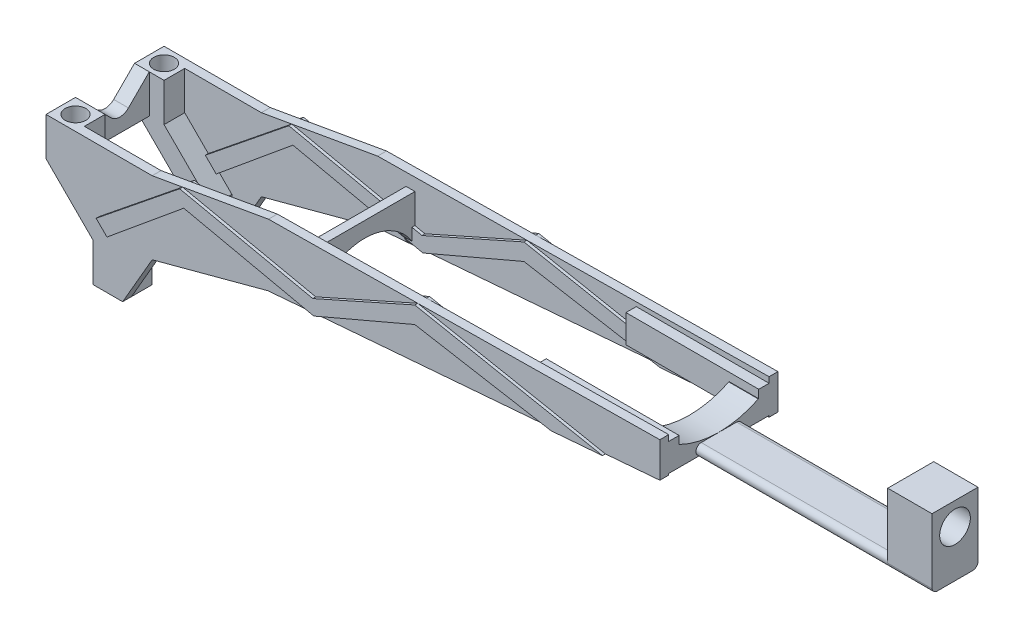
SolidWorks part; units mm, degrees
note: The reader was unsure of these and kept them because the rebuilt part matched: shared geometry of "草图5<8>", "草图18<3>", "草图24<4>".
ref_plane "前视基准面" through (0, 0, 0) normal (0, 0, 1) x (1, 0, 0)
ref_plane "上视基准面" through (0, 0, 0) normal (0, 1, 0) x (1, 0, 0)
ref_plane "右视基准面" through (0, 0, 0) normal (1, 0, 0) x (0, 0, -1)
sketch "草图1" plane through (0, 0, 0) normal (0, 0, 1) x (1, 0, 0)
  line L0 (0, 0) -> (0, -6.5)
  line L1 (0, -6.5) -> (7.9903, -14.4903)
  line L2 (7.9903, -14.4903) -> (7.9903, -20.9903)
  line L3 (7.9903, -20.9903) -> (12.9903, -20.9903)
  line L4 (12.9903, -20.9903) -> (12.9903, -14.4903)
  line L5 (12.9903, -14.4903) -> (5, -6.5)
  line L6 (5, -6.5) -> (5, 0)
  line L7 (0, 0) -> (5, 0)
extrude "凸台-拉伸1" add sketch "草图1" along normal blind 5 contours L7 L6 L5 L4 L3 L2 L1 L0
sketch "草图2" plane through (0, 0, 0) normal (0, 1, 0) x (1, 0, 0)
  line L0 (5, -5) -> (0, 0)
  line L3 (5, 0) -> (0, -5)
  circle A1 centre (2.5, -2.5) radius 1.75
extrude "切除-拉伸1" cut sketch "草图2" against normal blind 15
sketch "草图3" plane through (0, -20.9903, 0) normal (0, -1, 0) x (1, 0, 0)
  line L0 (7.9903, 5) -> (12.9903, 0)
  line L1 (12.9903, 5) -> (12.9903, 0) construction
  line L2 (7.9903, 0) -> (12.9903, 0) construction
  line L3 (7.9903, 0) -> (12.9903, 5)
  circle A1 centre (10.4903, 2.5) radius 1.75
sketch "草图5" plane through (0, 0, 5) normal (0, 0, 1) x (1, 0, 0)
  line L0 (12.9903, -20.9903) -> (17.9903, -12.3301)
  line L1 (17.9903, -12.3301) -> (37.5931, -7.0775)
  line L2 (37.5931, -7.0775) -> (107.0425, -1.4321)
  line L3 (5, 0) -> (17.9903, 0)
  line L4 (17.9903, 0) -> (37.6865, 3.473)
  line L5 (37.6865, 3.473) -> (107.0425, 4.3077)
  line L6 (107.0425, 4.3077) -> (107.0425, -1.4321)
  line L8 (87.8993, -2.9882) -> (94.7793, -2.429)
  line L14 (8.9952, -10.4952) -> (23.1388, 0.9078)
  line L17 (12.9903, -20.9903) -> (12.9903, -14.4903)
  line L18 (12.9903, -14.4903) -> (5, -6.5)
  line L19 (5, -6.5) -> (5, 0)
  line L20 (12.9903, -20.9903) -> (12.9903, -14.4903) construction
  line L22 (23.1388, 0.9078) -> (45.6985, -3.9198)
  line L23 (45.6985, -3.9198) -> (62.9747, 3.7773)
  line L24 (62.9747, 3.7773) -> (94.7793, -2.429)
  line L25 (10.8301, -12.3301) -> (23.8381, -1.5907)
  line L26 (23.8381, -1.5907) -> (45.8659, -6.405)
  line L27 (45.8659, -6.405) -> (62.9747, 0.9078)
  line L28 (62.9747, 0.9078) -> (86.0701, -3.1369)
extrude "凸台-拉伸2" add sketch "草图5" against normal blind 1.5 separate body
ref_plane "基准面5" through (0, 0, -10) normal (0, 0, -1) x (-1, 0, 0)
extrude "凸台-拉伸9" add sketch "草图5<8>" along normal blind 0.5 and the other way blind 2 contours L27 L28 L2 L24 L23 L22 L14 L18 L25 L26
sketch "草图5<8>" plane through (0, 0, 5) normal (0, 0, 1) x (1, 0, 0) same geometry as "草图5"
extrude "切除-拉伸6" cut sketch "草图3" against normal blind 6.5 contours A1
sketch "草图15" plane through (0, 0, -10) normal (0, 0, -1) x (-1, 0, 0)
  line L0 (-12.9903, -20.9903) -> (-7.9903, -20.9903)
  line L1 (-7.9903, -20.9903) -> (-7.9903, -14.4903)
  line L2 (-7.9903, -14.4903) -> (0, -6.5)
  line L3 (0, -6.5) -> (0, 0)
  line L4 (0, 0) -> (-5, 0)
  line L5 (-5, 0) -> (-17.9903, 0) construction
  line L6 (-5, -6.5) -> (-5, 0) construction
  line L7 (-5, 0) -> (-5, -6.5)
  line L8 (-5, -6.5) -> (-12.9903, -14.4903)
  line L9 (-12.9903, -14.4903) -> (-12.9903, -20.9903)
extrude "凸台-拉伸10" add sketch "草图15" along normal blind 5 separate body contours L9 L0 L1 L2 L3 L4 L7 L8
sketch "草图16" plane through (0, 0, 0) normal (0, 1, 0) x (1, 0, 0)
  line L0 (0, 15) -> (5, 10)
  line L1 (7.1447, 10) -> (-7.1447, 10) construction
  line L2 (5, 15) -> (5, 10) construction
  line L3 (5, 15) -> (0, 10)
  circle A0 centre (2.5, 12.5) radius 1.75
extrude "切除-拉伸7" cut sketch "草图16" against normal blind 15 contours L3 A0 L0 | L0 A0 L3 | L3 A0 L0 | L0 A0 L3
sketch "草图17" plane through (0, -20.9903, 0) normal (0, -1, 0) x (1, 0, 0)
  line L0 (7.9903, -15) -> (12.9903, -10)
  line L2 (-7.1447, -10) -> (7.1447, -10) construction
  line L3 (12.9903, -15) -> (7.9903, -10)
  circle A0 centre (10.4903, -12.5) radius 1.75
sketch "草图18" plane through (0, 0, -15) normal (0, 0, -1) x (-1, 0, 0)
  line L0 (-12.9903, -20.9903) -> (-17.9903, -12.3301)
  line L1 (-7.9903, -20.9903) -> (-12.9903, -20.9903) construction
  line L2 (-17.9903, -12.3301) -> (-37.5931, -7.0775)
  line L3 (-37.5931, -7.0775) -> (-107.0425, -1.4321)
  line L4 (-107.0425, -1.4321) -> (-107.0425, 4.3077)
  line L6 (-107.0425, 4.3077) -> (-37.6865, 3.473)
  line L7 (-37.6865, 3.473) -> (-17.9903, 0)
  line L8 (-17.9903, 0) -> (-5, 0)
  line L9 (-5, 0) -> (-5, -6.5)
  line L10 (-5, -6.5) -> (-12.9903, -14.4903)
  line L11 (-12.9903, -14.4903) -> (-12.9903, -20.9903)
  line L12 (-94.7793, -2.429) -> (-62.9747, 3.7773)
  line L13 (-62.9747, 3.7773) -> (-45.6985, -3.9198)
  line L14 (-45.6985, -3.9198) -> (-23.1388, 0.9078)
  line L15 (-23.1388, 0.9078) -> (-8.9952, -10.4952)
  line L16 (-86.0701, -3.1369) -> (-62.9747, 0.9078)
  line L17 (-62.9747, 0.9078) -> (-45.8659, -6.405)
  line L18 (-45.8659, -6.405) -> (-23.8381, -1.5907)
  line L19 (-23.8381, -1.5907) -> (-10.8301, -12.3301)
  line M11 (-5, -6.5) -> (-12.9903, -14.4903)
  line M12 (-12.9903, -14.4903) -> (-12.9903, -20.9903)
  line M18 (-5, 0) -> (-5, -6.5)
extrude "凸台-拉伸11" add sketch "草图18" against normal blind 1.5 contours L3 L12 L6 L4 | L17 L16 L3 | L13 L14 L7 L6 | L7 L15 L8 M11 M18 | L19 L18 L3 L2 L0 M12 M11
extrude "凸台-拉伸12" add sketch "草图18<3>" along normal blind 0.5 and the other way blind 2 contours L18 L19 L10 L15 L14 L13 L12 L3 L16 L17
sketch "草图18<3>" plane through (0, 0, -15) normal (0, 0, -1) x (-1, 0, 0) same geometry as "草图18"
extrude "切除-拉伸8" cut sketch "草图17" against normal blind 6.5 contours A0
sketch "草图19" plane through (0, 0, 0) normal (-1, 0, 0) x (0, 0, 1)
  line L0 (-10, 0) -> (-6.4645, -3.5355)
  line L1 (-10, 0) -> (-10, -6.5)
  line L2 (-10, 7.1447) -> (-10, -7.1447) construction
  line L3 (0, 0) -> (-3.5355, -3.5355)
  line L4 (-10, -6.5) -> (0, -6.5)
  line L5 (0, -6.5) -> (0, 0)
  arc A1 (-6.4645, -3.5355) -> (-3.5355, -3.5355) centre (-5, -2.0711) ccw
extrude "凸台-拉伸13" add sketch "草图19" against normal blind 2.5
ref_plane "基准面7" through (42.5, 0, 0) normal (1, 0, 0) x (0, 0, -1)
sketch "草图21" plane through (42.5, 0, 0) normal (1, 0, 0) x (0, 0, -1)
  line L0 (-3.5, 1.4378) -> (13.5, 1.4378)
  line L1 (-3.5, 4.3077) -> (-3.5, -1.4321) construction
  line L3 (13.5, -1.4321) -> (13.5, 4.3077) construction
  line L4 (-3.5, 1.4378) -> (-3.5, -6.5622)
  line L5 (-3.5, -6.405) -> (-3.5, -3.1369) construction
  line L6 (-3.5, -1.5907) -> (-3.5, -12.3301) construction
  line L7 (13.5, 1.4378) -> (13.5, -6.5622)
  line L8 (13.5, -1.5907) -> (13.5, -12.3301) construction
  line L9 (-3.5, -6.5622) -> (13.5, -6.5622)
  line L10 (5, -6.5622) -> (5, -10.5664)
  circle A0 centre (5, -10.5664) radius 9.408
extrude "凸台-拉伸14" add sketch "草图21" along normal blind 1.5 contours A0 L7 L0 L4
ref_plane "基准面8" through (104, 0, 0) normal (1, 0, 0) x (0, 0, -1)
sketch "草图24" plane through (104, 0, 0) normal (1, 0, 0) x (0, 0, -1)
  line L0 (-3.5, 1.9102) -> (13.5, 1.9102)
  line L1 (13.5, -2.429) -> (13.5, 3.7773) construction
  line L2 (13.5, 1.9102) -> (13.5, -1.4321)
  line L3 (-3.5, 4.3077) -> (-3.5, -1.4321) construction
  line L4 (-3.5, 1.9102) -> (-3.5, -1.4321)
  line L5 (-3.5, -1.4321) -> (13.5, -1.4321)
  line L6 (5, 1.9102) -> (5, 15.5602)
  line L7 (5, 1.9102) -> (-1.75, 1.9102)
  line L8 (-1.75, 1.9102) -> (5, 1.9102)
  line L9 (-3.5, 3.2744) -> (-3.5, -1.4321)
  line L10 (13.5, 3.2992) -> (11.75, 3.2992)
  line L11 (-3.5, 3.2744) -> (-1.75, 3.2744)
  line L12 (-1.75, 3.2744) -> (-1.75, -1.4321)
  line L13 (11.75, -1.4321) -> (13.5, -1.4321)
  line L14 (11.75, 3.2992) -> (11.75, -1.4321)
  line L15 (13.5, 3.2992) -> (13.5, 1.9102)
  circle A0 centre (5, 15.5602) radius 15.1949
extrude "凸台-拉伸15" add sketch "草图24" against normal blind 5 contours A0 L0 L4 L5 L2
extrude "凸台-拉伸16" add sketch "草图24<4>" against normal blind 22.5 contours L9 A0 L12 L11 | A0 L9 L0 L12 | L12 L0 L4 L5 | L0 L14 L5 L2 | A0 L14 L0 L15 | L14 A0 L15 L10
sketch "草图24<4>" plane through (104, 0, 0) normal (1, 0, 0) x (0, 0, -1) same geometry as "草图24"
sketch "草图26" plane through (104, 0, 0) normal (1, 0, 0) x (0, 0, -1)
  line L0 (2, 0.3579) -> (8, 0.3579)
  line L1 (2, -1.4321) -> (8, -1.4321)
  line L2 (-3.5, -1.4321) -> (13.5, -1.4321) construction
  arc A0 (2, -1.4321) -> (2, 0.3579) centre (2, -0.5371) cw
  arc A1 (8, 0.3579) -> (8, -1.4321) centre (8, -0.5371) cw
extrude "凸台-拉伸17" add sketch "草图26" along normal blind 40
sketch "草图28" plane through (104, 0, 0) normal (1, 0, 0) x (0, 0, -1)
  line L1 (-2.842, 4.5862) -> (-6.3038, 4.5862)
  line L2 (-2.842, 4.5862) -> (-2.842, -3.9587)
  line L3 (-2.842, -3.9587) -> (-6.3038, -3.9587)
  line L4 (-6.3038, 4.5862) -> (-6.3038, -3.9587)
  line L5 (12.6138, 4.5589) -> (15.9939, 4.5589)
  line L6 (12.6138, 4.5589) -> (12.6138, -3.9935)
  line L7 (12.6138, -3.9935) -> (15.9939, -3.9935)
  line L8 (15.9939, 4.5589) -> (15.9939, -3.9935)
extrude "切除-拉伸9" cut sketch "草图28" along normal blind 35
sketch "草图30" plane through (0, 0.3579, 0) normal (0, 1, 0) x (1, 0, 0)
  line L0 (144, 8.895) -> (104, 8.895) construction
  line L1 (136.5, 8.895) -> (144, 8.895)
  line L2 (136.5, 8.895) -> (136.5, 1.105)
  line L3 (136.5, 1.105) -> (144, 1.105)
  line L4 (144, 8.895) -> (144, 1.105)
extrude "凸台-拉伸18" add sketch "草图30" along normal blind 10 and the other way blind 1
sketch "草图31" plane through (136.5, 0, 0) normal (-1, 0, 0) x (0, 0, 1)
  circle A0 centre (-5, 6.5) radius 2.6
extrude "切除-拉伸10" cut sketch "草图31" against normal blind 7.5
